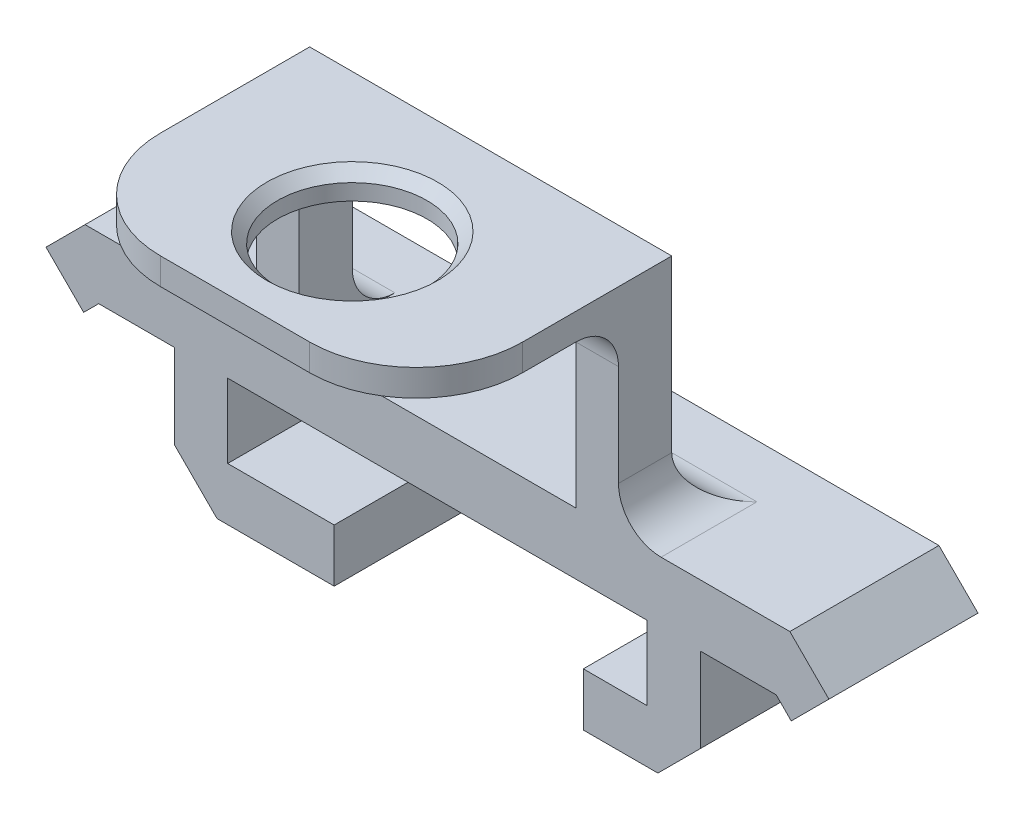
SolidWorks part; units mm, degrees
ref_plane "Front Plane" through (0, 0, 0) normal (0, 0, 1) x (1, 0, 0)
ref_plane "Top Plane" through (0, 0, 0) normal (0, 1, 0) x (1, 0, 0)
ref_plane "Right Plane" through (0, 0, 0) normal (1, 0, 0) x (0, 0, -1)
sketch "Sketch2" plane through (0, 0, 0) normal (0, 0, 1) x (1, 0, 0)
  line L0 (15.9053, 19.45) -> (-15.9053, 19.45)
  line L1 (16.5463, 22.3446) -> (-16.5463, 22.3446)
  line L2 (16.6106, 18.7411) -> (15.9053, 19.45)
  line L3 (18.3802, 20.5107) -> (16.5463, 22.3446)
  line L4 (-16.5463, 22.3446) -> (-18.3802, 20.5107)
  line L5 (-16.6124, 18.7429) -> (-15.9053, 19.45)
  line L6 (-16.6124, 18.7429) -> (-18.3802, 20.5107)
  line L7 (18.3802, 20.5107) -> (16.6106, 18.7411)
  dimension "D1" = 31.8107
  dimension "D2" = 2.8946
  dimension "D3" = 1
  dimension "D4" = 1
extrude "Boss-Extrude2" add sketch "Sketch2" along normal blind 5
extrude "Boss-Extrude3" add sketch "Sketch2<2>" against normal blind 2
sketch "Sketch2<2>" plane through (0, 0, 0) normal (0, 0, 1) x (1, 0, 0) same geometry as "Sketch2"
ref_plane "Plane1" through (19.4454, 19.4454, 0) normal (0.7071, 0.7071, 0) x (0.7071, -0.7071, 0)
ref_plane "Plane2" through (-19.4454, 19.4454, 0) normal (-0.7071, 0.7071, 0) x (0, 0, 1)
ref_plane "Plane4" through (0, 0, 5) normal (0, 0, 1) x (1, 0, 0)
ref_plane "Plane6" through (0, 19.45, 0) normal (0, -1, 0) x (-1, 0, 0)
sketch "Sketch8" plane through (0, 19.45, 0) normal (0, -1, 0) x (-1, 0, 0)
  line L1 (-8.5825, -5) -> (8.5825, -5) construction
  line L2 (12.35, 2) -> (9.85, 2)
  line L3 (15.9053, 2) -> (-15.9053, 2) construction
  line L4 (-9.85, 2) -> (-9.85, -5)
  line L5 (-9.85, -5) -> (-12.35, -5)
  line L6 (-12.35, -5) -> (-12.35, 2)
  line L7 (-12.35, 2) -> (-9.85, 2)
  line L8 (12.35, -5) -> (12.35, 2)
  line L9 (9.85, -5) -> (12.35, -5)
  line L10 (9.85, 2) -> (9.85, -5)
  point P0 (0, 0)
  dimension "D1" = 9.85
  dimension "D2" = 9.85
  dimension "D3" = 2.5
  dimension "D4" = 2.5
extrude "Boss-Extrude4" add sketch "Sketch8" along normal blind 5.96
ref_plane "Plane7" through (9.85, 0, 0) normal (-1, 0, 0) x (0, 0, 1)
sketch "Sketch10" plane through (9.85, 0, 0) normal (-1, 0, 0) x (0, 0, 1)
  line L0 (5, 13.49) -> (-2, 13.49) construction
  line L1 (5, 13.49) -> (-2, 13.49)
  line L2 (5, 13.49) -> (5, 15.98)
  line L3 (5, 15.98) -> (-2, 15.98)
  line L4 (-2, 13.49) -> (-2, 15.98)
  line L5 (-2, 13.49) -> (-2, 19.45) construction
  dimension "D1" = 2.49
extrude "Boss-Extrude5" add sketch "Sketch10" along normal blind 3
ref_plane "Plane8" through (-9.85, 0, 0) normal (1, 0, 0) x (0, 0, -1)
sketch "Sketch11" plane through (-9.85, 0, 0) normal (1, 0, 0) x (0, 0, -1)
  line L0 (2, 13.49) -> (2, 19.45) construction
  line L1 (-5, 13.49) -> (2, 13.49)
  line L2 (-5, 13.49) -> (-5, 15.98)
  line L3 (-5, 15.98) -> (2, 15.98)
  line L4 (2, 13.49) -> (2, 15.98)
  dimension "D1" = 2.49
extrude "Boss-Extrude6" add sketch "Sketch11" along normal blind 5
ref_plane "Plane9" through (0, 22.3446, 0) normal (0, 1, 0) x (1, 0, 0)
sketch "Sketch12" plane through (0, 22.3446, 0) normal (0, 1, 0) x (1, 0, 0)
  line L3 (16.5463, -5) -> (-16.5463, -5) construction
  line L4 (8.5, -5) -> (-8.5, -5)
  line L5 (8.5, -5) -> (8.5, -2.5)
  line L6 (8.5, -2.5) -> (-8.5, -2.5)
  line L7 (-8.5, -5) -> (-8.5, -2.5)
  point P6 (0, 0)
  dimension "D1" = 17
  dimension "D2" = 8.5
  dimension "D3" = 2.5
extrude "Boss-Extrude7" add sketch "Sketch12" along normal blind 10
ref_plane "Plane10" through (0, 0, 5) normal (0, 0, 1) x (1, 0, 0)
sketch "Sketch14" plane through (0, 0, 5) normal (0, 0, 1) x (1, 0, 0)
  line L0 (-8.5, 32.3446) -> (8.5, 32.3446) construction
  line L2 (-8.5, 22.3446) -> (-16.5463, 22.3446) construction
  line L7 (-6.5, 31.0946) -> (6.5, 31.0946)
  line L8 (-6.5, 31.0946) -> (-6.5, 22.3446)
  line L9 (-6.5, 22.3446) -> (6.5, 22.3446)
  line L10 (6.5, 31.0946) -> (6.5, 22.3446)
  dimension "D1" = 1.25
  dimension "D2" = 0
extrude "Cut-Extrude7" cut sketch "Sketch14" against normal up to next
sketch "Sketch16" plane through (0, 0, 5) normal (0, 0, 1) x (1, 0, 0)
  line L0 (8.5, 32.3446) -> (8.5, 22.3446) construction
  line L1 (-8.5, 32.3446) -> (8.5, 32.3446)
  line L2 (-8.5, 32.3446) -> (-8.5, 31.0946)
  line L3 (-8.5, 31.0946) -> (8.5, 31.0946)
  line L4 (8.5, 32.3446) -> (8.5, 31.0946)
  dimension "D1" = 1.25
extrude "Boss-Extrude8" add sketch "Sketch16" along normal blind 9.5
ref_plane "Plane11" through (0, 32.3446, 0) normal (0, 1, 0) x (1, 0, 0)
sketch "Sketch17" plane through (0, 32.3446, 0) normal (0, 1, 0) x (1, 0, 0)
  line L0 (8.5, -14.5) -> (-8.5, -14.5) construction
  line L1 (-8.5, -2.5) -> (-8.5, -14.5) construction
  circle A0 centre (0, -9) radius 3.51
  dimension "D1" = 5.5
  dimension "D2" = 8.5
extrude "Cut-Extrude8" cut sketch "Sketch17" against normal up to next
fillet "Fillet7" radius 2 1 edges
fillet "Fillet8" radius 5 1 edges at (8.5, 31.7196, 14.5)
fillet "Fillet9" radius 5 1 edges at (-8.5, 31.7196, 14.5)
chamfer "Chamfer1" distance 2 angle 45 1 edges at (-12.35, 13.49, 1.5)
chamfer "Chamfer2" distance 2 angle 45 1 edges at (12.35, 13.49, 1.5)
ref_plane "Plane13" through (0, 0, 2.5) normal (0, 0, -1) x (-1, 0, 0)
sketch "Sketch22" plane through (0, 0, 2.5) normal (0, 0, -1) x (-1, 0, 0)
  line L1 (6.5, 22.3446) -> (8.5, 22.3446)
  line L2 (6.5, 22.3446) -> (6.5, 32.3446)
  line L3 (6.5, 32.3446) -> (8.5, 32.3446)
  line L4 (8.5, 22.3446) -> (8.5, 32.3446)
  line L5 (-6.5, 22.3446) -> (-8.5, 22.3446)
  line L6 (-6.5, 22.3446) -> (-6.5, 32.3446)
  line L7 (-6.5, 32.3446) -> (-8.5, 32.3446)
  line L8 (-8.5, 22.3446) -> (-8.5, 32.3446)
ref_plane "Plane14" through (-8.5, 0, 0) normal (-1, 0, 0) x (0, 0, 1)
fillet "Fillet11" radius 2 1 edges
fillet "Fillet12" radius 2 1 edges
fillet "Fillet13" radius 2 1 edges at (8.5, 22.3446, 2.5)
fillet "Fillet14" radius 2 1 edges at (-8.5, 22.3446, 2.5)
fillet "Fillet16" radius 2 1 edges
chamfer "Chamfer3" distance 0.5 angle 45 1 edges at (0, 32.3446, 12.51)
